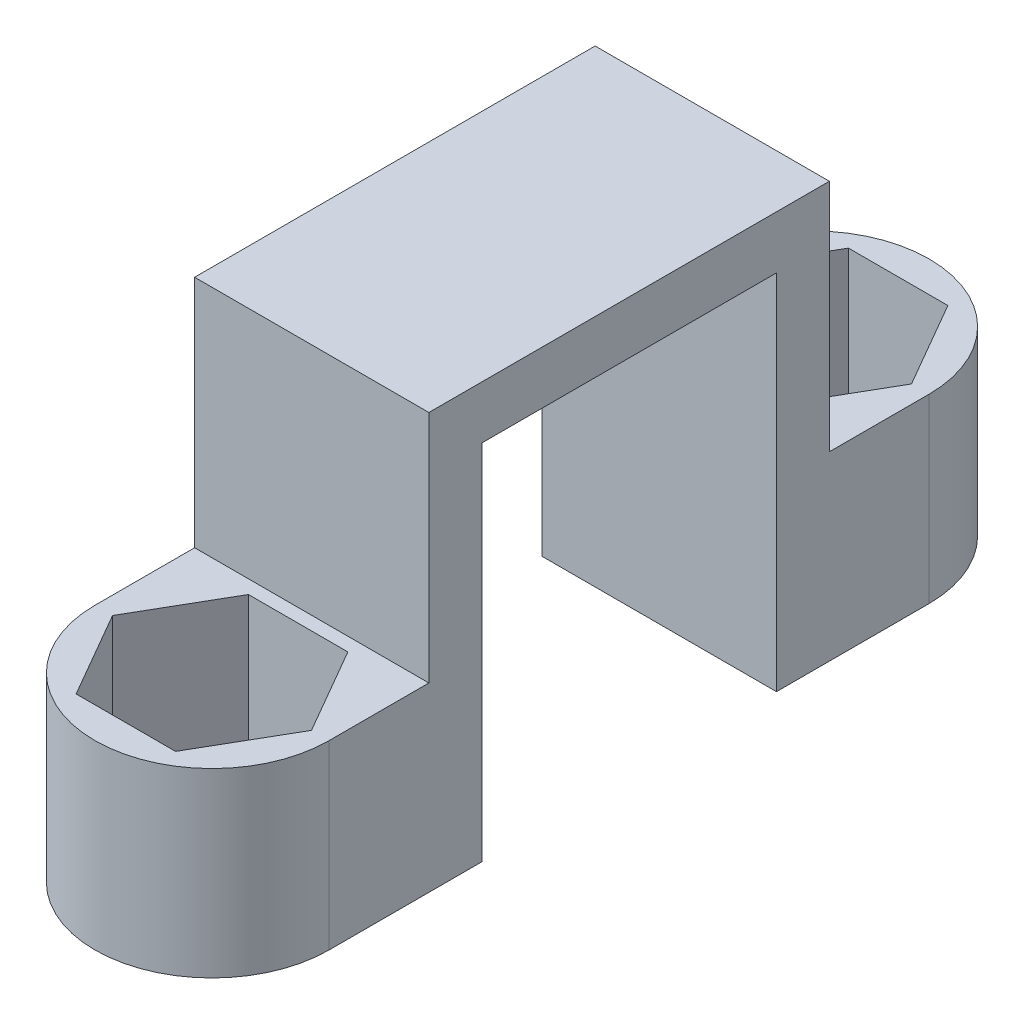
SolidWorks part; units mm, degrees
ref_plane "Přední rovina" through (0, 0, 0) normal (0, 0, 1) x (1, 0, 0)
ref_plane "Horní rovina" through (0, 0, 0) normal (0, 1, 0) x (1, 0, 0)
ref_plane "Pravá rovina" through (0, 0, 0) normal (1, 0, 0) x (0, 0, -1)
sketch "Sketch1" plane through (0, 0, 0) normal (1, 0, 0) x (0, 0, -1)
  line L0 (-4.875, 5.125) -> (-4.875, -6.875)
  line L1 (-6.625, 6.875) -> (6.625, 6.875)
  line L2 (-6.625, 6.875) -> (-6.625, -6.875)
  line L3 (-6.625, -6.875) -> (6.625, -6.875)
  line L4 (6.625, 6.875) -> (6.625, -6.875)
  line L5 (-6.625, 6.875) -> (6.625, -6.875) construction
  line L6 (-6.625, -6.875) -> (6.625, 6.875) construction
  line L7 (-4.875, 5.125) -> (4.875, 5.125)
  line L8 (4.875, 5.125) -> (4.875, -6.875)
  point P0 (0, 0)
  dimension "D1" = 1.75
  dimension "D2" = 1.75
  dimension "D3" = 1.75
  dimension "D4" = 9.75
  dimension "D5" = 12
extrude "Boss-Extrude1" add sketch "Sketch1" along normal blind 7.75 contours L7 L8 L3 L4 L1 L2 L0 region at (0, -0.875, 5.066)
sketch "Sketch2" plane through (0, -6.875, 0) normal (0, -1, 0) x (1, 0, 0)
  line L0 (3.875, 4.875) -> (3.875, 9.925) construction
  line L1 (0, 6.625) -> (0, 4.875) construction
  line L2 (0, 4.875) -> (0, 9.925)
  line L3 (7.75, 4.875) -> (7.75, 9.925)
  line L4 (7.75, 4.875) -> (0, 4.875) construction
  line L5 (7.75, 6.625) -> (7.75, 4.875) construction
  line L6 (7.75, 6.625) -> (0, 6.625) construction
  line L7 (7.75, 4.875) -> (0, 4.875)
  line L8 (2.2296, 12.775) -> (0.5841, 9.925)
  line L9 (0.5841, 9.925) -> (2.2296, 7.075)
  line L10 (2.2296, 7.075) -> (5.5204, 7.075)
  line L11 (5.5204, 7.075) -> (7.1659, 9.925)
  line L12 (7.1659, 9.925) -> (5.5204, 12.775)
  line L13 (5.5204, 12.775) -> (2.2296, 12.775)
  line L14 (0, 6.625) -> (0, -6.625) construction
  arc A0 (0, 4.875) -> (7.75, 4.875) centre (3.875, 4.875) ccw
  arc A1 (7.75, 9.925) -> (0, 9.925) centre (3.875, 9.925) ccw
  circle A3 centre (3.875, 9.925) radius 2.85 construction
  point P4 (3.875, 7.4)
  point P28 (0, 0)
  line M9 (7.75, 6.625) -> (0, 6.625)
  dimension "D1" = 5.7
  dimension "D3" = 9.925
  dimension "D2" = 3.3
extrude "Boss-Extrude2" add sketch "Sketch2" against normal blind 5 from offset 1 contours L3 A1 L2 M9 region at (0.1056, -6.875, 8.275) offset against normal yes
sketch "Sketch3" plane through (0, -5.875, 0) normal (0, -1, 0) x (1, 0, 0)
  line L0 (7.75, 6.625) -> (0, 6.625) construction
  line L1 (7.75, 6.625) -> (7.75, 9.925) construction
  line L2 (0, 6.625) -> (0, 9.925) construction
  line L3 (7.75, 6.625) -> (0, 6.625)
  line L4 (7.75, 6.625) -> (7.75, 9.925)
  line L5 (0, 6.625) -> (0, 9.925)
  arc A0 (7.75, 9.925) -> (0, 9.925) centre (3.875, 9.925) ccw construction
  arc A1 (7.75, 9.925) -> (0, 9.925) centre (3.875, 9.925) ccw
  circle A2 centre (3.875, 9.925) radius 1.6
  dimension "D1" = 3.2
extrude "Boss-Extrude3" add sketch "Sketch3" along normal up to surface (1 mm away) up to face at (3.875, -6.875, 5.75)
mirror "Mirror1" about plane through (0, 0, 0) normal (0, 0, 1) of "Boss-Extrude3", "Boss-Extrude2"
